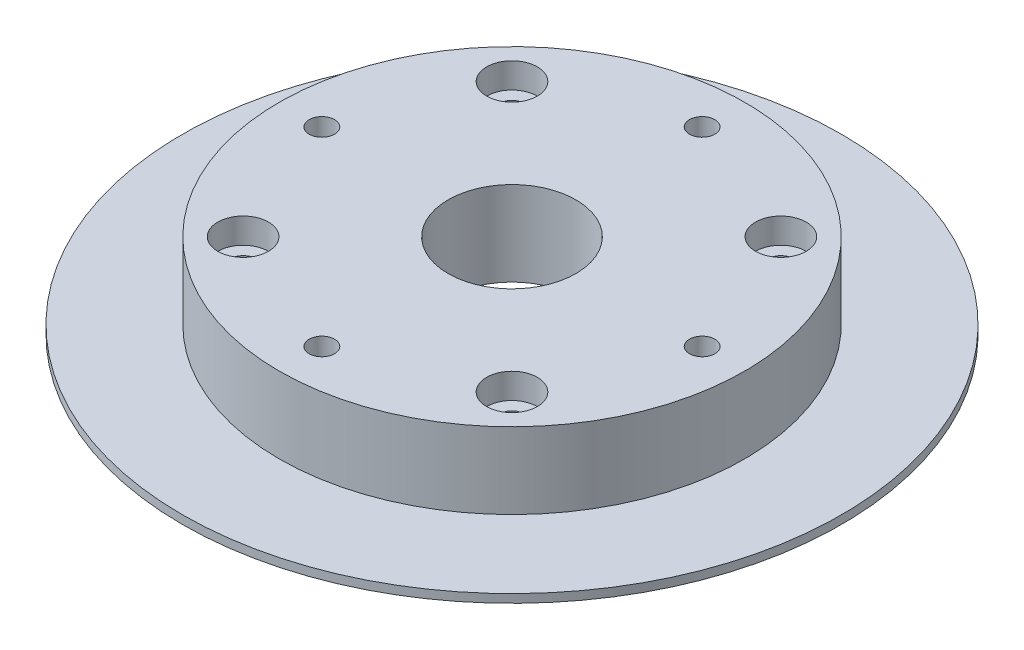
SolidWorks part; units mm, degrees
ref_plane "Front Plane" through (0, 0, 0) normal (0, 0, 1) x (1, 0, 0)
ref_plane "Top Plane" through (0, 0, 0) normal (0, 1, 0) x (1, 0, 0)
ref_plane "Right Plane" through (0, 0, 0) normal (1, 0, 0) x (0, 0, -1)
sketch "Sketch1" plane through (0, 0, 0) normal (0, 1, 0) x (1, 0, 0)
  line L0 (0, 0) -> (22.5, 0) construction
  circle A0 centre (0, 0) radius 39
  circle A1 centre (22.5, 0) radius 1.5
  circle A2 centre (15.9099, -15.9099) radius 1.5
  circle A3 centre (0, -22.5) radius 1.5
  circle A4 centre (-15.9099, -15.9099) radius 1.5
  circle A5 centre (-22.5, 0) radius 1.5
  circle A6 centre (-15.9099, 15.9099) radius 1.5
  circle A7 centre (0, 22.5) radius 1.5
  circle A8 centre (15.9099, 15.9099) radius 1.5
  circle A9 centre (0, 0) radius 7.5635
  circle A10 centre (0, 0) radius 27.55
  point P14 (0, 0)
  dimension "D2" = 78
  dimension "D3" = 15.127
  dimension "D5" = 3
  dimension "D6" = 55.1
  dimension "D4" = 22.5
  dimension "D1" = 8
extrude "Boss-Extrude1" add sketch "Sketch1" against normal blind 1 contours A0 A10 | A10 A2 A3 A4 A5 A6 A7 A8 A9 A1 region at (-37.8969, 0, 0) region at (-26.7708, 0, 0)
extrude "Boss-Extrude2" add sketch "Sketch1<3>" along normal blind 9 contours A10 A2 A3 A4 A5 A6 A7 A8 A9 A1 region at (-26.7708, 0, 0)
sketch "Sketch1<3>" plane through (0, 0, 0) normal (0, 1, 0) x (1, 0, 0) same geometry as "Sketch1"
sketch "Sketch2" plane through (0, 9, 0) normal (0, 1, 0) x (1, 0, 0)
  circle A0 centre (15.9099, 15.9099) radius 3
  circle A1 centre (15.9099, -15.9099) radius 3
  circle A2 centre (-15.9099, -15.9099) radius 3
  circle A3 centre (-15.9099, 15.9099) radius 3
  point P3 (-12.79, 21.6127)
  point P4 (0, 0)
  point P12 (0, 0)
  circle M4 centre (-15.9099, -15.9099) radius 1.5
  circle M6 centre (-15.9099, 15.9099) radius 1.5
  circle M8 centre (15.9099, 15.9099) radius 1.5
  dimension "D1" = 6
  dimension "D2" = 4
extrude "Cut-Extrude1" cut sketch "Sketch2" against normal blind 3 contours A3 M6 | A0 M8 | A2 M4 | A1 region at (12.9948, 9, -15.9099) region at (-18.825, 9, 15.9099) region at (-18.825, 9, -15.9099)
equation "\"bearing_21_OD\"= 21mm"
equation "\"pin_cirlce_diameter\"= 75mm"
equation "\"pin_diam\"= 6mm"
equation "\"gear_thickness\"= 4mm"
equation "\"ball_bearing_diam\"= 2.96mm"
equation "\"bearing_21_outer_clearance\"= 0mm'change this"
equation "\"bearing_15_OD\"= 15mm"
equation "\"bearing_15_outer_clearance\"= 0mm'change this"
equation "\"thrust_bearing_thickness\"= 5mm'measure this irl and change"
equation "\"D3@Sketch1\"=\"bearing_15_OD\" + 0.127mm"
equation "\"D1@Boss-Extrude2\"=\"thrust_bearing_thickness\"+4mm"
